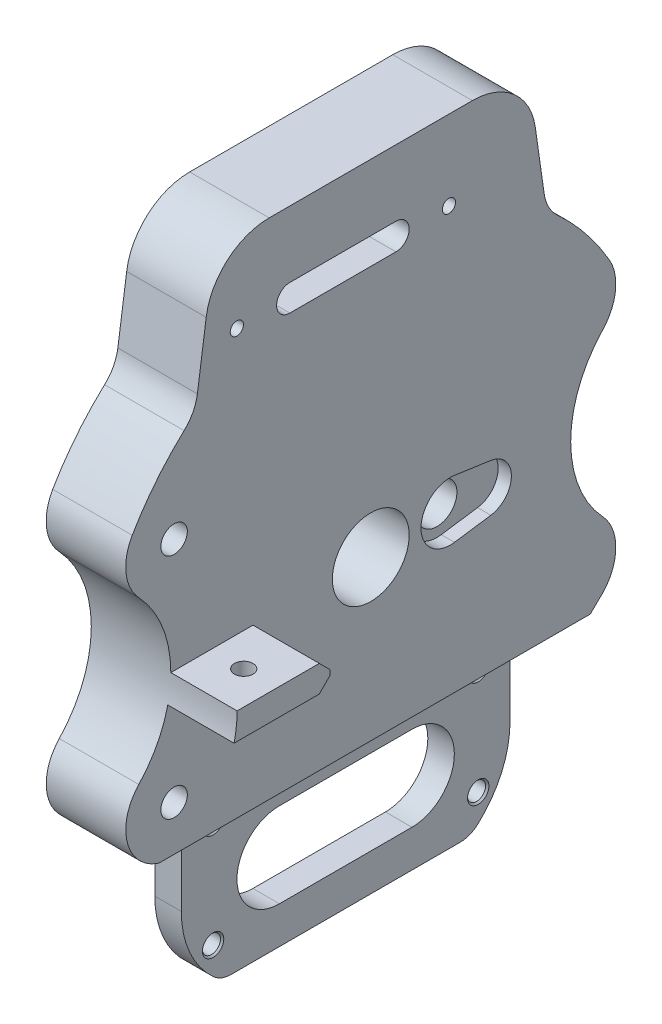
SolidWorks part; units mm, degrees
ref_plane "Płaszczyzna przednia" through (0, 0, 0) normal (0, 0, 1) x (1, 0, 0)
ref_plane "Płaszczyzna górna" through (0, 0, 0) normal (0, 1, 0) x (1, 0, 0)
ref_plane "Płaszczyzna prawa" through (0, 0, 0) normal (1, 0, 0) x (0, 0, -1)
sketch "Szkic1" plane through (0, 0, 0) normal (1, 0, 0) x (0, 0, -1)
  line L0 (-14.4695, -100) -> (35.5305, -100) construction
  line L1 (-14.4695, -84) -> (35.5305, -84)
  line L2 (-14.4695, -116) -> (35.5305, -116)
  line L3 (0, 0) -> (0, -130.3815) construction
  line L4 (0, 0) -> (-120, 0) construction
  line L5 (0, 0) -> (0, 195.8303) construction
  line L6 (13.6636, -130) -> (-20.5826, 195.8303) construction
  line L7 (-30.5104, 100) -> (9.4896, 100) construction
  line L8 (-30.5104, 105) -> (9.4896, 105) construction
  line L9 (-30.5104, 95) -> (9.4896, 95) construction
  line L19 (62.0766, 109.386) -> (65.4007, 86.06)
  line L20 (38.3166, 130) -> (-38.3166, 130)
  line L21 (-62.0766, 109.386) -> (-65.4007, 86.06)
  line L28 (-14.4695, -130) -> (35.5305, -130)
  line L33 (10.5305, -100) -> (10.5305, -46.7527) construction
  line L35 (-14.4695, -130) -> (-32.6078, -130)
  line L38 (-51.4695, -100) -> (-51.4695, -70)
  line L39 (35.5305, -130) -> (53.6689, -130)
  line L40 (-51.4695, -70) -> (-81.2407, -59.5241)
  line L41 (72.5305, -100) -> (72.5305, -70)
  line L43 (72.5305, -70) -> (85.8486, -57.0401)
  circle A0 centre (0, 0) radius 14.5
  arc A1 (-14.4695, -84) -> (-14.4695, -116) centre (-14.4695, -100) ccw
  arc A2 (35.5305, -116) -> (35.5305, -84) centre (35.5305, -100) ccw
  circle A3 centre (0, 0) radius 85.75 construction
  arc A4 (-30.5104, 105) -> (-30.5104, 95) centre (-30.5104, 100) ccw construction
  arc A5 (9.4896, 95) -> (9.4896, 105) centre (9.4896, 100) ccw construction
  circle A24 centre (-74.1894, 43) radius 5
  circle A25 centre (-74.1894, -43) radius 5
  arc A32 (87.4958, -30.51) -> (85.8486, -57.0401) centre (74.1894, -43) cw
  arc A33 (87.4958, -30.51) -> (87.4958, 30.51) centre (120, 0) cw
  arc A34 (89.9789, 52.1516) -> (87.4958, 30.51) centre (74.1894, 43) cw
  arc A35 (70.4086, 76.5417) -> (89.9789, 52.1516) centre (0, 0) cw
  arc A36 (65.4007, 86.06) -> (70.4086, 76.5417) centre (81.2407, 88.3174) ccw
  arc A37 (38.3166, 130) -> (62.0766, 109.386) centre (38.3166, 106) cw
  arc A38 (-38.3166, 130) -> (-62.0766, 109.386) centre (-38.3166, 106) ccw
  arc A39 (-65.4007, 86.06) -> (-70.4086, 76.5417) centre (-81.2407, 88.3174) cw
  arc A40 (-70.4086, 76.5417) -> (-89.9789, 52.1516) centre (0, 0) ccw
  arc A41 (-89.9789, 52.1516) -> (-87.4958, 30.51) centre (-74.1894, 43) ccw
  arc A42 (-87.4958, -30.51) -> (-87.4958, 30.51) centre (-120, 0) ccw
  arc A43 (-87.4958, -30.51) -> (-81.2407, -59.5241) centre (-74.4106, -42.8703) ccw
  arc A55 (60.3868, -127.4074) -> (72.5305, -100) centre (35.5305, -100) ccw
  arc A58 (-51.4695, -100) -> (-39.3257, -127.4074) centre (-14.4695, -100) ccw
  arc A59 (60.3868, -127.4074) -> (53.6689, -130) centre (53.6689, -120) cw
  arc A64 (-32.6078, -130) -> (-39.3257, -127.4074) centre (-32.6078, -120) cw
  point P5 (10.5305, -100)
  point P12 (-74.1894, -43)
  point P13 (-74.1894, 43)
  point P19 (-10.5104, 100)
  point P24 (-25, -70)
  point P25 (25, -70)
  point P30 (25, -100)
  point P31 (25, -130)
  point P33 (-25, -130)
  point P34 (-25, -100)
  point P41 (-25, -70)
  point P42 (25, -70)
  point P43 (-25.5104, 81)
  point P44 (25, -100)
  point P46 (-25, -130)
  point P47 (-25, -100)
  point P49 (62, -82.8995)
  point P52 (46.6564, -130)
  point P57 (-46.6564, -130)
  point P58 (62, -100)
  point P59 (25, -100)
  point P60 (25, -137)
  point P61 (-25, -137)
  point P62 (-25, -100)
  point P63 (-62, -100)
  point P64 (-62, -82.8995)
  point P72 (0, 126)
  dimension "D1" = 29
  dimension "D3" = 16
  dimension "D5" = 86
  dimension "D7" = 171.5
  dimension "D9" = 40
  dimension "D10" = 5
  dimension "D18" = 120
  dimension "D13" = 60
  dimension "D14" = 10
  dimension "D12" = 18
  dimension "D2" = 50
  dimension "D4" = 100
  dimension "D6" = 43
  dimension "D8" = 6
  dimension "D11" = 100
extrude "Dodanie-wyciągnięcie1" add sketch "Szkic1" along normal mid plane 30
hole_wizard "M6 Tapped Hole1" positions "Sketch1" profile "Sketch2" tap size "M6" standard "ISO" end condition through all
sketch "Sketch1" plane through (15, 0, 0) normal (1, 0, 0) x (0, 0, -1)
  line L0 (-81.7008, 100) -> (63.4141, 100) construction
  line L2 (0, 0) -> (0, 150.2111) construction
  line L4 (65.4007, 86.06) -> (62.0766, 109.386) construction
  line L5 (38.3166, 130) -> (-38.3166, 130) construction
  line L7 (-10.5104, 105) -> (-10.5104, 95) construction
  line L8 (9.4896, 105) -> (-30.5104, 105) construction
  line L9 (-30.5104, 95) -> (9.4896, 95) construction
  point P0 (-50.5104, 100)
  point P2 (29.4896, 100)
  dimension "D1" = 40
  dimension "D2" = 40
  dimension "D3" = 30
sketch "Sketch2" plane through (15, 100, 50.5104) normal (0, 1, 0) x (0, 0, -1)
  line L0 (0, 0) -> (0, 30)
  line L1 (0, 30) -> (2.5, 30)
  line L2 (2.5, 30) -> (2.5, 0)
  line L5 (2.5, 0) -> (0, 0)
  line L11 (0, -6.35) -> (0, 107.95) construction
  dimension "Thru Tap Drill Dia." = 5
  dimension "Thru Tap Drill Depth" = 30
cosmetic thread "Hole Thread1" parameters "D2"=6
cosmetic thread "Hole Thread2" parameters "D2"=6
sketch "Szkic4" plane through (-15, 0, 0) normal (-1, 0, 0) x (0, 0, 1)
  line L0 (30.5104, 105) -> (-9.4896, 105) construction
  line L1 (30.5104, 105) -> (-9.4896, 105)
  line L2 (30.5104, 95) -> (-9.4896, 95) construction
  line L3 (30.5104, 95) -> (-9.4896, 95)
  arc A0 (30.5104, 95) -> (30.5104, 105) centre (30.5104, 100) ccw construction
  arc A1 (30.5104, 95) -> (30.5104, 105) centre (30.5104, 100) ccw
  arc A2 (-9.4896, 105) -> (-9.4896, 95) centre (-9.4896, 100) ccw construction
  arc A3 (-9.4896, 105) -> (-9.4896, 95) centre (-9.4896, 100) ccw
sketch "Szkic5" plane through (15, 0, 0) normal (-1, 0, 0) x (0, 0, 1)
  line L0 (0, 0) -> (75.42, 0) construction
  line L2 (75.42, 0) -> (44.42, 0)
  line L4 (76.556, -10) -> (44.42, -10)
  line L5 (40.42, -4) -> (40.42, -6)
  line L6 (44.42, 0) -> (40.42, -4)
  line L7 (40.42, -6) -> (44.42, -10)
  arc A0 (87.4958, 30.51) -> (87.4958, -30.51) centre (120, 0) ccw construction
  arc A1 (75.42, 0) -> (76.556, -10) centre (120, 0) ccw
  point P3 (40.42, -10)
  point P5 (40.42, 0)
  dimension "D1" = 10
  dimension "D2" = 35
extrude "Dodanie-wyciągnięcie3" add sketch "Szkic5" against normal blind 25 contours L2 L6 L5 L7 L4 A1
hole_wizard "Otwór gwintowany M8x1.01" positions "Szkic10" profile "Szkic11" tap size "M8x1.0" standard "ISO"
sketch "Szkic10" plane through (0, 0, 0) normal (0, 1, 0) x (1, 0, 0)
  line L2 (40, -75.42) -> (40, -44.42) construction
  line L3 (40, -75.42) -> (15, -75.42) construction
  point P8 (27.5, -60.42)
  dimension "D3" = 12.5
  dimension "D4" = 15
sketch "Szkic11" plane through (27.5, 0, 60.42) normal (1, 0, 0) x (0, 0, 1)
  line L0 (0, 0) -> (0, 21)
  line L1 (0, 21) -> (3.5, 18.897)
  line L2 (3.5, 18.897) -> (3.5, 0)
  line L5 (3.5, 0) -> (0, 0)
  line L10 (0, 21) -> (-3.5, 18.897) construction
  line L11 (0, -6.35) -> (0, 107.95) construction
  dimension "Średnica wiertła gwintu" = 7
  dimension "Głębokość otworu gwintowanego" = 21
  dimension "Kąt wiertła" = 118
sketch "Szkic12" plane through (15, 0, 0) normal (1, 0, 0) x (0, 0, -1)
  line L2 (9.4896, 105) -> (-30.5104, 105)
  line L3 (-30.5104, 95) -> (9.4896, 95)
  line L4 (9.4896, 105) -> (-30.5104, 105)
  line L5 (-30.5104, 95) -> (9.4896, 95)
  arc A2 (9.4896, 95) -> (9.4896, 105) centre (9.4896, 100) ccw
  arc A3 (-30.5104, 105) -> (-30.5104, 95) centre (-30.5104, 100) ccw
  arc A4 (9.4896, 95) -> (9.4896, 105) centre (9.4896, 100) ccw
  arc A5 (-30.5104, 105) -> (-30.5104, 95) centre (-30.5104, 100) ccw
  dimension "D1" = 0
extrude "Wytnij-wyciągnięcie2" cut sketch "Szkic12" against normal blind 10 contours A5 L5 A4 L4
sketch "Szkic16" plane through (15, 0, 0) normal (1, 0, 0) x (0, 0, -1)
  line L0 (-14.4695, -116) -> (35.5305, -116) construction
  line L1 (35.5305, -84) -> (-14.4695, -84) construction
  line L3 (-32.6078, -130) -> (53.6689, -130) construction
  line L5 (-14.4695, -116) -> (35.5305, -116)
  line L6 (35.5305, -84) -> (-14.4695, -84)
  line L8 (-32.6078, -130) -> (53.6689, -130)
  line L9 (-51.4695, -70) -> (-51.4695, -100) construction
  line L10 (-62, -100) -> (62, -100) construction
  line L11 (-51.4695, -70) -> (72.5305, -70)
  line L13 (-51.4695, -70) -> (-51.4695, -100)
  line L16 (72.5305, -70) -> (72.5305, -100)
  arc A0 (-14.4695, -84) -> (-14.4695, -116) centre (-14.4695, -100) ccw construction
  arc A1 (35.5305, -116) -> (35.5305, -84) centre (35.5305, -100) ccw construction
  arc A3 (53.6689, -130) -> (60.3868, -127.4074) centre (53.6689, -120) ccw construction
  arc A4 (-39.3257, -127.4074) -> (-32.6078, -130) centre (-32.6078, -120) ccw construction
  arc A6 (-14.4695, -84) -> (-14.4695, -116) centre (-14.4695, -100) ccw
  arc A7 (35.5305, -116) -> (35.5305, -84) centre (35.5305, -100) ccw
  arc A9 (53.6689, -130) -> (60.3868, -127.4074) centre (53.6689, -120) ccw
  arc A10 (-39.3257, -127.4074) -> (-32.6078, -130) centre (-32.6078, -120) ccw
  arc A18 (60.3868, -127.4074) -> (72.5305, -100) centre (35.5305, -100) ccw construction
  arc A19 (-51.4695, -100) -> (-39.3257, -127.4074) centre (-14.4695, -100) ccw construction
  arc A20 (60.3868, -127.4074) -> (72.5305, -100) centre (35.5305, -100) ccw
  arc A21 (-51.4695, -100) -> (-39.3257, -127.4074) centre (-14.4695, -100) ccw
extrude "Wytnij-wyciągnięcie4" cut sketch "Szkic16" against normal blind 20
chamfer "Sfazowanie4" distance 10 angle 45 1 edges at (15, -70, -10.5305)
sketch "Szkic17" plane through (15, 0, 0) normal (1, 0, 0) x (0, 0, -1)
  line L4 (31.5786, -10.9367) -> (45.2929, -8.9572)
  line L5 (45.2929, 8.9572) -> (31.5786, 10.9367)
  arc A4 (31.5786, 10.9367) -> (18.9801, -0.8154) centre (30, 0) ccw
  arc A5 (18.9801, -0.8154) -> (31.5786, -10.9367) centre (30, 0) ccw
  circle A6 centre (30, 0) radius 7.5
  arc A11 (45.2929, -8.9572) -> (45.2929, 8.9572) centre (44, 0) ccw
  point P0 (8.9572, 38.7071)
  point P1 (-0.6678, 49.0253)
  point P3 (-8.9572, 38.7071)
  point P5 (-6.9777, 24.9929)
  point P6 (0, 26)
  point P7 (4.5988, 31.3435)
  point P8 (0, 26)
  point P9 (6.9777, 24.9929)
  point P21 (0, 26)
  point P22 (5.9035, 32.8594)
  dimension "D1" = 14
  dimension "D2" = 30
extrude "Wytnij-wyciągnięcie5" cut sketch "Szkic17" against normal blind 5 contours L4 A11 L5 A4 A5
extrude "Wytnij-wyciągnięcie6" cut sketch "Szkic17<5>" against normal through all contours A6
sketch "Szkic17<5>" plane through (15, 0, 0) normal (1, 0, 0) x (0, 0, -1) same geometry as "Szkic17"
sketch "Szkic18" plane through (-5, 0, 0) normal (1, 0, 0) x (0, 0, -1)
  line L0 (10.5305, -84) -> (10.5305, -116) construction
  line L1 (35.5305, -84) -> (-14.4695, -84) construction
  line L2 (-14.4695, -116) -> (35.5305, -116) construction
  line L3 (-30.4695, -100) -> (51.5305, -100) construction
  arc A0 (-14.4695, -84) -> (-14.4695, -116) centre (-14.4695, -100) ccw construction
  arc A1 (35.5305, -116) -> (35.5305, -84) centre (35.5305, -100) ccw construction
  point P14 (-39.4695, -77)
  point P17 (60.5305, -77)
  point P18 (60.5305, -117)
  point P19 (-39.4695, -117)
  dimension "D1" = 23
  dimension "D2" = 50
  dimension "D3" = 2
  dimension "D4" = 2
hole_wizard "Otwór gwintowany M81" positions "Szkic 3D1" profile "Szkic19" tap size "M8" standard "ISO"
sketch3d "Szkic 3D1"
  point P0 (-5, -77, 39.4695)
  point P3 (-5, -117, 39.4695)
  point P6 (-5, -117, -60.5305)
  point P9 (-5, -77, -60.5305)
sketch "Szkic19" plane through (-5, -77, 39.4695) normal (0, 1, 0) x (0, 0, -1)
  line L0 (0, 0) -> (0, 18.25)
  line L1 (0, 18.25) -> (3.4, 16.2071)
  line L2 (3.4, 16.2071) -> (3.4, 0.625)
  line L3 (3.4, 0.625) -> (4.025, 0)
  line L5 (4.025, 0) -> (0, 0)
  line L6 (-3.4, 0.625) -> (-4.025, 0) construction
  line L10 (0, 18.25) -> (-3.4, 16.2071) construction
  line L11 (0, -6.35) -> (0, 107.95) construction
  dimension "Średnica wiertła gwintu" = 6.8
  dimension "Głębokość otworu gwintowanego" = 18.25
  dimension "Średnica zewnętrznego pogłębienia stożkowego" = 8.05
  dimension "Kąt zewnętrznego pogłębienia stożkowego" = 90
  dimension "Kąt wiertła" = 118
cosmetic thread "Gwint otworu1" parameters "D1"=10, "D2"=8
cosmetic thread "Gwint otworu2" parameters "D1"=10, "D2"=8
cosmetic thread "Gwint otworu3" parameters "D1"=10, "D2"=8
cosmetic thread "Gwint otworu4" parameters "D1"=10, "D2"=8
